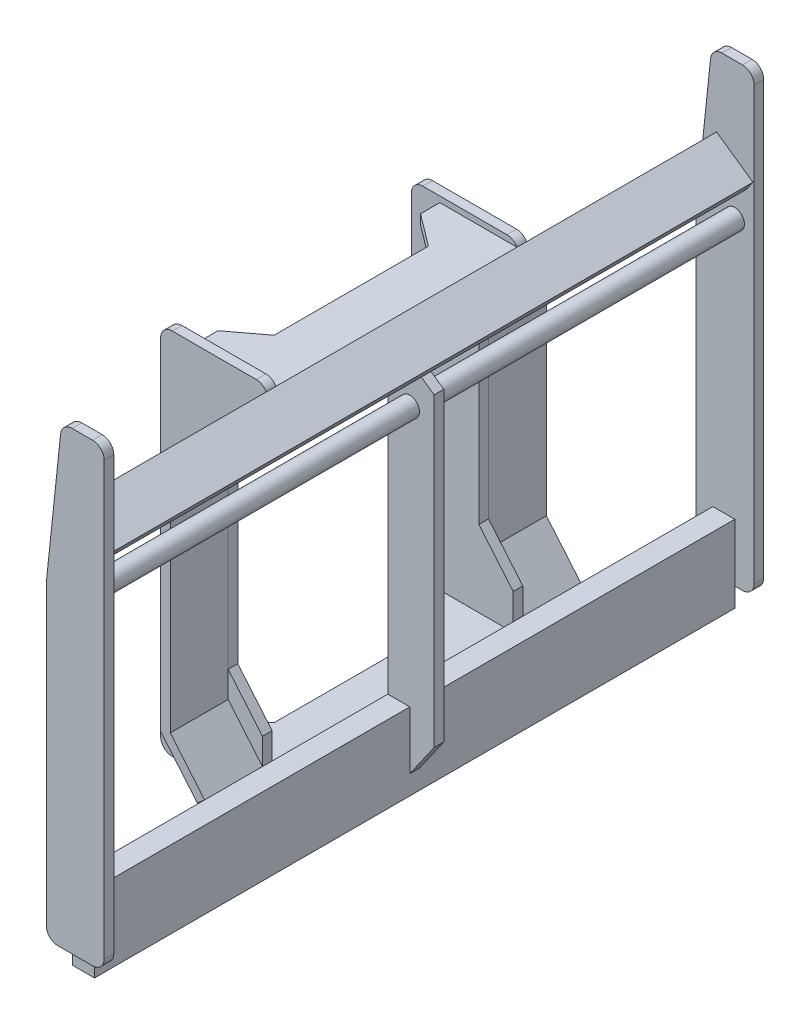
SolidWorks part; units mm, degrees
ref_plane "Front Plane" through (0, 0, 0) normal (0, 0, 1) x (1, 0, 0)
ref_plane "Top Plane" through (0, 0, 0) normal (0, 1, 0) x (1, 0, 0)
ref_plane "Right Plane" through (0, 0, 0) normal (1, 0, 0) x (0, 0, -1)
sketch "Sketch1" plane through (0, 0, 0) normal (0, 0, 1) x (1, 0, 0)
  line L0 (0, 0) -> (0, 1180)
  line L1 (0, 0) -> (-150, 0)
  line L2 (-150, 0) -> (-150, 800)
  line L3 (-150, 800) -> (-110, 1180)
  line L4 (-110, 1180) -> (0, 1180)
  dimension "D1" = 1180
  dimension "D2" = 150
  dimension "D3" = 110
  dimension "D4" = 800
extrude "Boss-Extrude1" add sketch "Sketch1" along normal blind 25 from offset 830
extrude "Boss-Extrude2" add sketch "Sketch1<2>" against normal blind 25 from offset 830 separate body offset against normal yes
sketch "Sketch1<2>" plane through (0, 0, 0) normal (0, 0, 1) x (1, 0, 0) same geometry as "Sketch1"
sketch "Sketch2" plane through (0, 0, -830) normal (0, 0, 1) x (1, 0, 0)
  line L0 (-3, 930) -> (-20.2073, 905.4254)
  line L1 (-107, 150) -> (-50, 150)
  line L2 (-107, 150) -> (-107, -50)
  line L3 (-107, -50) -> (-50, -50)
  line L4 (-50, 150) -> (-50, -50)
  line L5 (-3, 930) -> (-97.2025, 995.9613)
  line L6 (-20.2073, 905.4254) -> (-114.4098, 971.3867)
  line L7 (-97.2025, 995.9613) -> (-114.4098, 971.3867)
  line L8 (0, 0) -> (0, 1180) construction
  line L9 (0, 1180) -> (-110, 1180) construction
  line L10 (-150, 0) -> (0, 0) construction
  dimension "D1" = 30
  dimension "D2" = 115
  dimension "D3" = 3
  dimension "D4" = 55
  dimension "D5" = 250
  dimension "D6" = 57
  dimension "D7" = 50
  dimension "D8" = 150
  dimension "D9" = 200
extrude "Boss-Extrude3" add sketch "Sketch2" along normal up to surface (1660 mm away) up to face at (-82, 632, 830)
sketch "Sketch3" plane through (0, 0, 0) normal (0, 0, 1) x (1, 0, 0)
  line L0 (-107, 966.1983) -> (13, 882.1734)
  line L5 (13, 882.1734) -> (13, 89.9733)
  line L6 (13, 89.9733) -> (-50, 0)
  line L7 (-50, 0) -> (-50, 150) construction
  line L8 (-50, 0) -> (-50, 150)
  line L9 (-50, 150) -> (-107, 150)
  line L10 (-107, 150) -> (-107, 0) construction
  line L11 (-50, 150) -> (-107, 150) construction
  line L12 (-107, 150) -> (-107, 966.1983)
  line L13 (-50, 0) -> (0, 0) construction
  line L14 (-114.4098, 971.3867) -> (-20.2073, 905.4254) construction
  dimension "D1" = 120
  dimension "D2" = 150
  dimension "D3" = 55
  dimension "D4" = 0
extrude "Boss-Extrude4" add sketch "Sketch3" along normal mid plane 25
sketch "Sketch4" plane through (0, 0, 855) normal (0, 0, 1) x (1, 0, 0)
  line L0 (0, 0) -> (0, 1180) construction
  line L1 (0, 1180) -> (-110, 1180) construction
  circle A0 centre (-50, 825) radius 25
  dimension "D1" = 50
  dimension "D2" = 50
  dimension "D3" = 355
extrude "Cut-Extrude1" cut sketch "Sketch4" against normal through all
sketch "Sketch5" plane through (0, 0, 855) normal (0, 0, 1) x (1, 0, 0)
  circle A0 centre (-50, 825) radius 25 construction
  circle A1 centre (-50, 825) radius 25
extrude "Boss-Extrude5" add sketch "Sketch5" against normal up to surface (1710 mm away) up to face at (-25, 825, -855)
sketch "Sketch7" plane through (0, 0, -12.5) normal (0, 0, -1) x (-1, 0, 0)
  line L0 (114.4098, 971.3867) -> (97.2025, 995.9613) construction
  line L1 (20.2073, 905.4254) -> (114.4098, 971.3867) construction
  line L2 (107, 150) -> (50, 150) construction
  line L3 (107, 0) -> (107, 150) construction
  line L4 (114.4098, 971.3867) -> (97.2025, 995.9613)
  line L5 (20.2073, 905.4254) -> (114.4098, 971.3867)
  line L6 (107, 150) -> (50, 150)
  line L7 (107, 0) -> (107, 150)
  line L8 (97.2025, 995.9613) -> (97.2025, 1010.9613)
  line L9 (97.2025, 1010.9613) -> (371, 1010.9613)
  line L10 (371, 1010.9613) -> (371, 52.9613)
  line L11 (371, 52.9613) -> (107, 75)
  line L12 (107, 75) -> (107, 150)
  line L13 (50, 150) -> (196, 323.996)
  line L14 (196, 323.996) -> (196, 822.5318)
  line L15 (196, 822.5318) -> (67.3085, 938.4061)
  line L16 (107, 966.1983) -> (107, 150) construction
  line M6 (107, 150) -> (107, 966.1983)
  dimension "D1" = 77
  dimension "D2" = 50
  dimension "D3" = 175
  dimension "D4" = 89
  dimension "D5" = 15
  dimension "D6" = 958
extrude "Boss-Extrude6" add sketch "Sketch7" along normal blind 25 from offset 300 contours L15 L14 L13 L7 L11 L10 L9 L8 L4 L5 M6 region at (-263.4879, 530.0956, -12.5)
sketch "Sketch8" plane through (0, 0, -337.5) normal (0, 0, -1) x (-1, 0, 0)
  line L0 (107, 150) -> (196, 256.0661)
  line L1 (196, 256.0661) -> (196, 859.7532)
  line L2 (196, 859.7532) -> (107, 934.433)
  line L3 (107, 902.6677) -> (107, 966.1983) construction
  line L4 (196, 323.996) -> (196, 822.5318) construction
  dimension "D1" = 130
  dimension "D2" = 140
  dimension "D3" = 0
extrude "Extrude-Thin1" add sketch "Sketch8" along normal blind 150 separate body thin thin type one direction wall 25
sketch "Sketch9" plane through (397.3283, 333.398, 0) normal (0.766, 0.6428, 0) x (0, 0, -1)
  line L4 (337.5, 809.5955) -> (337.5, 784.5955)
  line L5 (337.5, 784.5955) -> (487.5, 784.5955)
  line L6 (487.5, 784.5955) -> (487.5, 809.5955)
  line L7 (487.5, 809.5955) -> (337.5, 809.5955)
  line L8 (337.5, 809.5955) -> (337.5, 784.5955)
  line L9 (337.5, 784.5955) -> (487.5, 784.5955)
  line L10 (487.5, 784.5955) -> (487.5, 809.5955)
  line L11 (487.5, 809.5955) -> (337.5, 809.5955)
  dimension "D1" = 0
extrude "Boss-Extrude7" add sketch "Sketch9" along normal up to next separate body
mirror "Mirror5" about plane through (0, 0, 0) normal (0, 0, 1) of bodies 108 109 107
ref_plane "Plane2" through (0, 995.9613, 0) normal (0, 1, 0) x (-1, 0, 0)
sketch "Sketch11" plane through (0, 995.9613, 0) normal (0, 1, 0) x (-1, 0, 0)
  line L0 (297.2025, 312.5) -> (97.2025, 312.5)
  line L1 (97.2025, 312.5) -> (371, 312.5) construction
  line L2 (97.2025, 312.5) -> (97.2025, -312.5)
  line L3 (97.2025, -830) -> (97.2025, 312.5) construction
  line L4 (97.2025, -312.5) -> (371, -312.5) construction
  line L5 (97.2025, -312.5) -> (297.2025, -312.5)
  line L6 (297.2025, -312.5) -> (297.2025, -262.5)
  line L7 (297.2025, -262.5) -> (214.4098, -200)
  line L8 (214.4098, -200) -> (214.4098, 200)
  line L9 (214.4098, 200) -> (297.2025, 262.5)
  line L10 (297.2025, 262.5) -> (297.2025, 312.5)
  line L11 (114.4098, -830) -> (114.4098, 312.5) construction
  line L12 (0, 0) -> (400, 0) construction
  dimension "D1" = 100
  dimension "D2" = 50
  dimension "D3" = 200
  dimension "D4" = 400
extrude "Boss-Extrude8" add sketch "Sketch11" against normal blind 25
pattern_linear "LPattern1" count 2 spacing 870 along (0, -1, 0) of "Boss-Extrude8"
fillet "Fillet1" radius 30 14 edges at (-97.2025, 1010.9613, -325) (-97.2025, 1010.9613, 325) (-371, 1010.9613, -325) (-110, 1180, 842.5) (0, 1180, 842.5) (-110, 1180, -842.5) (0, 1180, -842.5) (0, 0, -842.5) (0, 0, 842.5) (-150, 0, 842.5) (-371, 52.9613, 325) (-371, 1010.9613, 325) (-150, 0, -842.5) (-371, 52.9613, -325)
